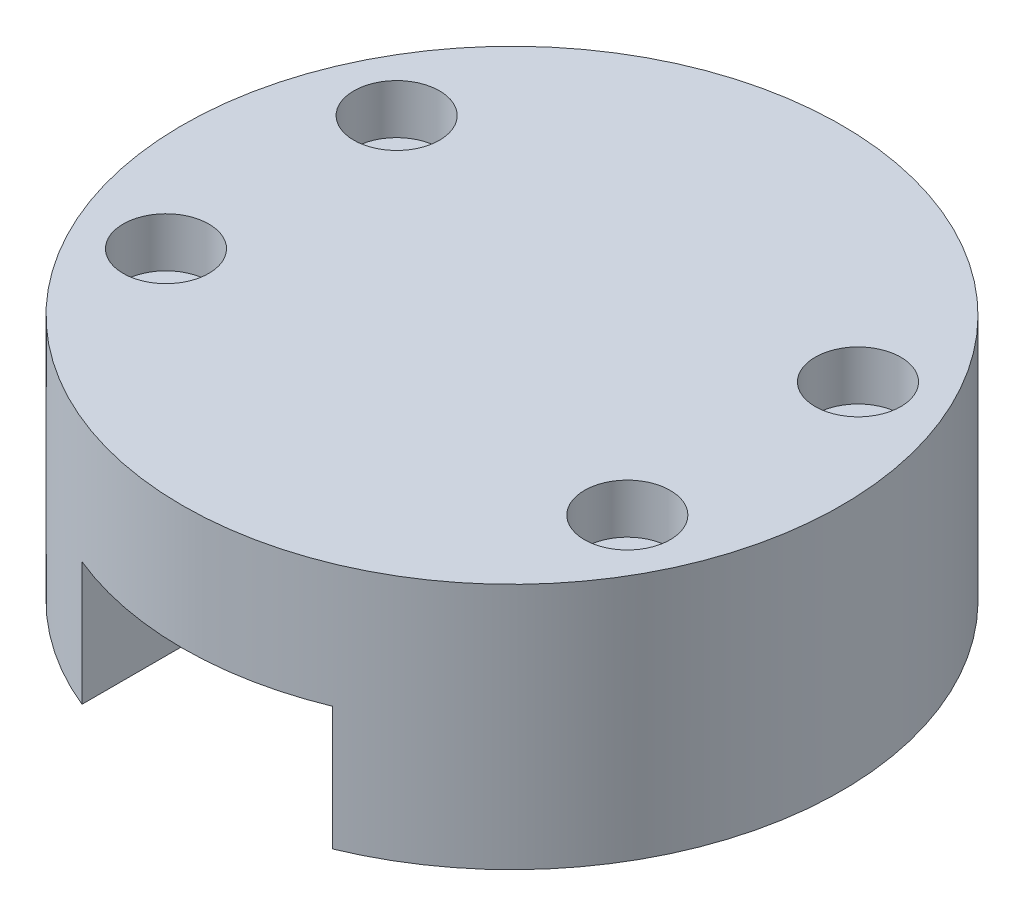
SolidWorks part; units mm, degrees
ref_plane "Front Plane" through (0, 0, 0) normal (0, 0, 1) x (1, 0, 0)
ref_plane "Top Plane" through (0, 0, 0) normal (0, 1, 0) x (1, 0, 0)
ref_plane "Right Plane" through (0, 0, 0) normal (1, 0, 0) x (0, 0, -1)
sketch "Sketch1" plane through (0, 0, 0) normal (0, 1, 0) x (1, 0, 0)
  circle A0 centre (0, 0) radius 20
  dimension "D1" = 40
extrude "Boss-Extrude1" add sketch "Sketch1" along normal blind 15
sketch "Sketch2" plane through (0, 0, 0) normal (0, 0, 1) x (1, 0, 0)
  line L4 (-7.6, 0) -> (-7.6, 7.5)
  line L5 (-20, 0) -> (20, 0) construction
  line L6 (-7.6, 7.5) -> (7.6, 7.5)
  line L7 (7.6, 7.5) -> (7.6, 0)
  line L8 (7.6, 0) -> (-7.6, 0)
  dimension "D1" = 15.2
  dimension "D2" = 7.5
  dimension "D3" = 7.6
extrude "Cut-Extrude1" cut sketch "Sketch2" against normal blind 25 and the other way blind 25
sketch "Sketch3" plane through (0, 0, 0) normal (0, -1, 0) x (-1, 0, 0)
  circle A0 centre (14, -7) radius 1.5
  circle A1 centre (14, 7) radius 1.5
  circle A2 centre (-14, -7) radius 1.5
  circle A3 centre (-14, 7) radius 1.5
  dimension "D1" = 3
  dimension "D2" = 3
  dimension "D3" = 3
  dimension "D4" = 3
  dimension "D5" = 14
  dimension "D6" = 14
  dimension "D7" = 7
  dimension "D8" = 14
  dimension "D9" = 14
  dimension "D10" = 28
  dimension "D11" = 7
extrude "Cut-Extrude2" cut sketch "Sketch3" against normal up to next
sketch "Sketch4" plane through (0, 15, 0) normal (0, 1, 0) x (1, 0, 0)
  circle A0 centre (-14, 7) radius 2.6
  circle A1 centre (-14, -7) radius 2.6
  circle A2 centre (14, 7) radius 2.6
  circle A3 centre (14, -7) radius 2.6
  dimension "D1" = 5.2
  dimension "D2" = 5.2
  dimension "D3" = 5.2
  dimension "D4" = 5.2
extrude "Cut-Extrude3" cut sketch "Sketch4" against normal blind 3
